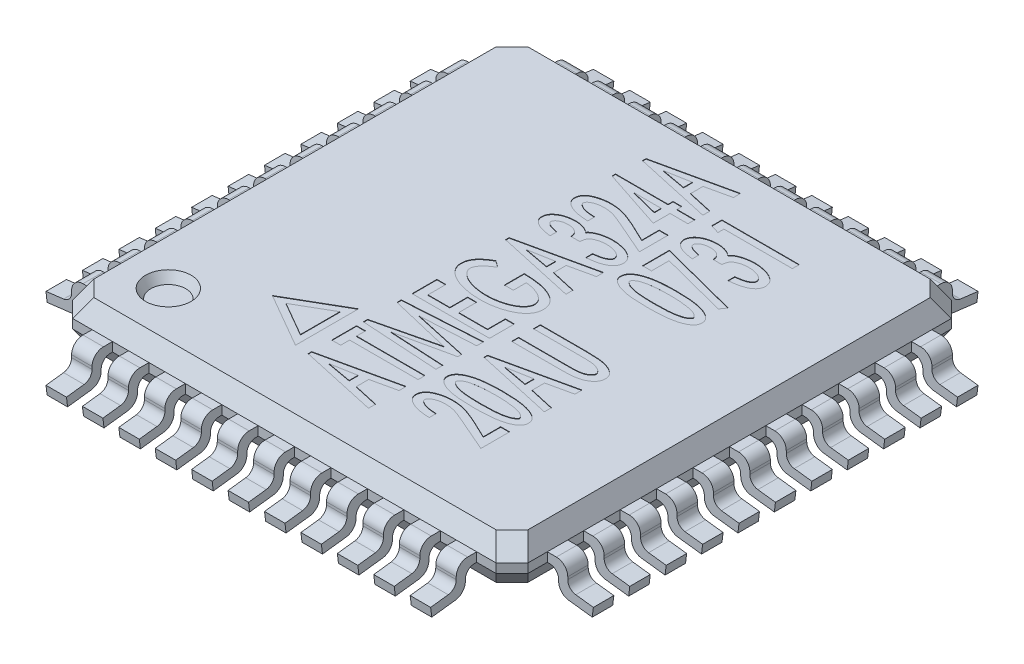
SolidWorks part; units mm, degrees
ref_plane "Спереди" through (0, 0, 0) normal (0, 0, 1) x (1, 0, 0)
ref_plane "Сверху" through (0, 0, 0) normal (0, 1, 0) x (1, 0, 0)
ref_plane "Справа" through (0, 0, 0) normal (1, 0, 0) x (0, 0, -1)
sketch "Эскиз1" plane through (0, 0, 0) normal (0, 1, 0) x (1, 0, 0)
  line L1 (-5, -5) -> (5, -5)
  line L2 (-5, -5) -> (-5, 5)
  line L3 (-5, 5) -> (5, 5)
  line L4 (5, -5) -> (5, 5)
  line L5 (-5, -5) -> (5, 5) construction
  line L6 (-5, 5) -> (5, -5) construction
  point P0 (0, 0)
  dimension "D1" = 5
  dimension "D2" = 5
extrude "Бобышка-Вытянуть1" add sketch "Эскиз1" along normal blind 1
ref_plane "Плоскость1" through (4, 0, 0) normal (1, 0, 0) x (0, 0, -1)
sketch "Эскиз4" plane through (4, 0, 0) normal (1, 0, 0) x (0, 0, -1)
  line L0 (-5, 0.6) -> (-5.2, 0.6)
  line L1 (-5, 1) -> (-5, 0) construction
  line L2 (-5.45, 0.35) -> (-5.45, 0.2945)
  line L3 (-5.6256, 0.096) -> (-6.0122, 0.0485)
  line L4 (-6.0122, 0.0485) -> (-5.9878, -0.15)
  line L5 (-5.9878, -0.15) -> (-5.4695, -0.0864)
  line L6 (-5.25, 0.1618) -> (-5.25, 0.2)
  line L7 (-5.05, 0.4) -> (-5, 0.4)
  line L8 (-5, 0.4) -> (-5, 0.6)
  line L9 (-5, 0.5) -> (-5.4165, 0.5) construction
  line L10 (-5, 0) -> (5, 0) construction
  line L11 (-6, -0.0507) -> (-5.4299, 0.0193) construction
  arc A0 (-5.45, 0.35) -> (-5.2, 0.6) centre (-5.2, 0.35) cw
  arc A1 (-5.25, 0.2) -> (-5.05, 0.4) centre (-5.05, 0.2) cw
  arc A2 (-5.4695, -0.0864) -> (-5.25, 0.1618) centre (-5.5, 0.1618) ccw
  arc A3 (-5.6256, 0.096) -> (-5.45, 0.2945) centre (-5.65, 0.2945) ccw
  dimension "D9" = 0.25
  dimension "D10" = 0.2
  dimension "D11" = 0.25
  dimension "D12" = 0.2
  dimension "D1" = 0.1
  dimension "D2" = 0.25
  dimension "D3" = 0.75
  dimension "D4" = 0.2
  dimension "D5" = 0.5
  dimension "D6" = 0.2
  dimension "D7" = 0.15
  dimension "D8" = 7
extrude "Бобышка-Вытянуть2" add sketch "Эскиз4" along normal mid plane 0.45 separate body
pattern_linear "Линейный массив1" count 11 spacing 0.8 along (-1, 0, 0) of "Бобышка-Вытянуть2"
ref_plane "Плоскость2" through (0, 0, 0) normal (0, 0, -1) x (-1, 0, 0)
mirror "Зеркальное отражение1" about plane through (0, 0, 0) normal (0, 0, -1) of "Бобышка-Вытянуть2", "Линейный массив1"
ref_plane "Плоскость3" through (0, 0, 4) normal (0, 0, 1) x (1, 0, 0)
sketch "Эскиз6" plane through (0, 0, 4) normal (0, 0, 1) x (1, 0, 0)
  line L0 (-5, 0.6) -> (-5.2, 0.6)
  line L2 (-5.45, 0.35) -> (-5.45, 0.2945)
  line L3 (-5.6256, 0.096) -> (-6.0122, 0.0485)
  line L4 (-6.0122, 0.0485) -> (-5.9878, -0.15)
  line L5 (-5.9878, -0.15) -> (-5.4695, -0.0864)
  line L6 (-5.25, 0.1618) -> (-5.25, 0.2)
  line L7 (-5.05, 0.4) -> (-5, 0.4)
  line L8 (-5, 0.4) -> (-5, 0.6)
  line L9 (-5, 0.5) -> (-5.4165, 0.5) construction
  line L11 (-6, -0.0507) -> (-6.4151, -0.1017) construction
  line L12 (-5, 1) -> (-5, 0) construction
  arc A0 (-5.45, 0.35) -> (-5.2, 0.6) centre (-5.2, 0.35) cw
  arc A1 (-5.25, 0.2) -> (-5.05, 0.4) centre (-5.05, 0.2) cw
  arc A2 (-5.4695, -0.0864) -> (-5.25, 0.1618) centre (-5.5, 0.1618) ccw
  arc A3 (-5.6256, 0.096) -> (-5.45, 0.2945) centre (-5.65, 0.2945) ccw
  dimension "D9" = 0.25
  dimension "D10" = 0.2
  dimension "D11" = 0.25
  dimension "D12" = 0.2
  dimension "D1" = 0.1
  dimension "D2" = 0.25
  dimension "D3" = 0.75
  dimension "D4" = 0.2
  dimension "D5" = 0.45
  dimension "D6" = 0.2
  dimension "D8" = 7
extrude "Бобышка-Вытянуть3" add sketch "Эскиз6" along normal mid plane 0.45 separate body
pattern_linear "Линейный массив2" count 11 spacing 0.8 along (0, 0, -1) of "Бобышка-Вытянуть3"
ref_plane "Плоскость4" through (0, 0, 0) normal (1, 0, 0) x (0, 0, -1)
mirror "Зеркальное отражение2" about plane through (0, 0, 0) normal (1, 0, 0) of "Бобышка-Вытянуть3", "Линейный массив2"
chamfer "Фаска5" distance 0.4 angle 30 4 edges at (0, 1, -5) (5, 1, 0) (0, 1, 5) (-5, 1, 0)
chamfer "Фаска6" distance 0.4 angle 30 4 edges at (0, 0, -5) (5, 0, 0) (0, 0, 5) (-5, 0, 0)
chamfer "Фаска9" distance 0.35 4 edges at (5, 0.5, 5) (5, 0.5, -5) (-5, 0.5, -5) (-5, 0.5, 5)
chamfer "Фаска10" distance 0.313 8 edges at (4.797, 0.0484, 4.797) (-4.797, 0.0484, -4.797) (-4.797, 0.0484, 4.797) (4.797, 0.0484, -4.797) (4.797, 0.9516, 4.797) (-4.797, 0.9516, 4.797) (-4.797, 0.9516, -4.797) (4.797, 0.9516, -4.797)
sketch "Эскиз7" plane through (0, 1, 0) normal (0, 1, 0) x (1, 0, 0)
  line L0 (-4.275, -3.775) -> (-3.275, -3.775) construction
  line L1 (-5, -3.775) -> (-5.2, -3.775) construction
  line L2 (-3.775, -3.275) -> (-3.775, -4.275) construction
  line L3 (-3.775, -5) -> (-3.775, -5.2) construction
  circle A0 centre (-3.775, -3.775) radius 0.5
  dimension "D1" = 1
extrude "Вырез-Вытянуть1" cut sketch "Эскиз7" against normal blind 0.2 draft 30
sketch "Эскиз8" plane through (0, 1, 0) normal (0, 1, 0) x (1, 0, 0)
  line L0 (-1.2951, -3.4619) -> (-1.2951, -2.0762)
  line L1 (2.7049, -4.7691) -> (2.7049, 4.7691) construction
  line L4 (-1.2951, -4.7691) -> (-1.2951, 4.7691) construction
  line L5 (-1.2951, -2.0762) -> (-2.4951, -2.7691)
  line L6 (-2.4951, -2.7691) -> (-1.2951, -3.4619)
  line L7 (0.7049, -4.7691) -> (0.7049, 4.7691) construction
  line L8 (-1.4451, -2.336) -> (-2.1951, -2.7691)
  line L9 (-2.1951, -2.7691) -> (-1.4451, -3.2021)
  line L10 (-1.4451, -2.336) -> (-1.4451, -3.2021)
  line L12 (-4.4191, -4.7691) -> (4.4191, -4.7691) construction
  line L13 (4.4191, 4.7691) -> (-4.4191, 4.7691) construction
  text T0 "<b>ATMEGA324A</b>" font "Century Gothic" height 1.7
  text T1 "<b>20AU    0731</b>" font "Century Gothic" height 1.7
  dimension "D1" = 60
  dimension "D2" = 60
  dimension "D3" = 1.2
  dimension "D4" = 1
  dimension "D5" = 1
  dimension "D6" = 0.15
  dimension "D7" = 0.15
  dimension "D8" = 0.15
  dimension "D9" = 2
  dimension "D10" = 2
extrude "Вырез-Вытянуть3" cut sketch "Эскиз8" against normal blind 0.01
